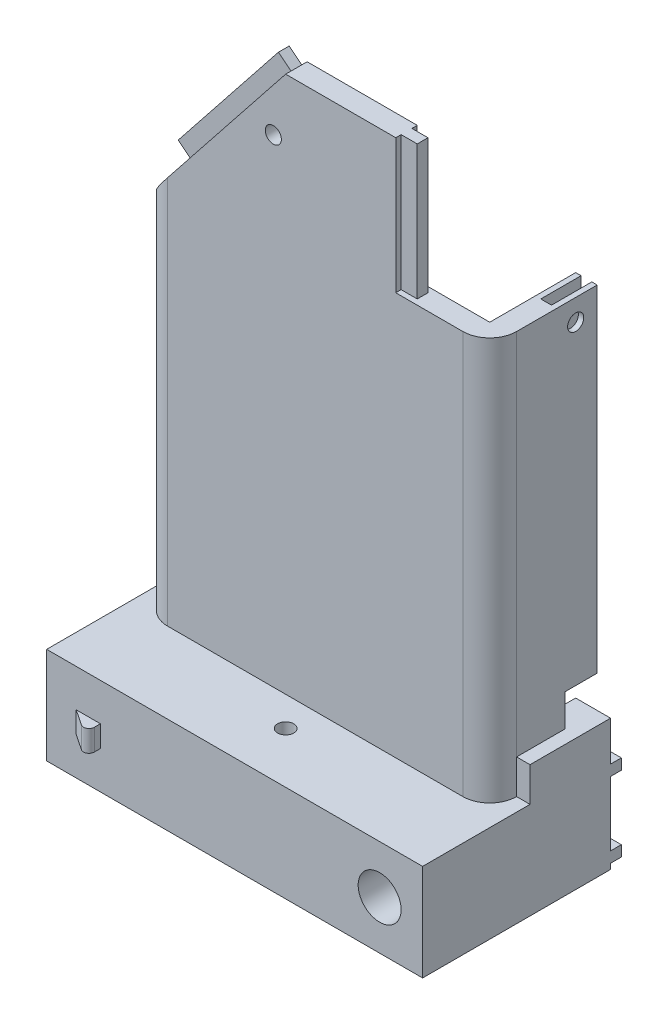
SolidWorks part; units mm, degrees
ref_plane "Front Plane" through (0, 0, 0) normal (0, 0, 1) x (1, 0, 0)
ref_plane "Top Plane" through (0, 0, 0) normal (0, 1, 0) x (1, 0, 0)
ref_plane "Right Plane" through (0, 0, 0) normal (1, 0, 0) x (0, 0, -1)
sketch "Sketch1" plane through (0, 0, 0) normal (0, 1, 0) x (1, 0, 0)
  line L1 (-32.5, -20) -> (32.5, -20)
  line L2 (-32.5, -20) -> (-32.5, 20)
  line L3 (-32.5, 20) -> (32.5, 20)
  line L4 (32.5, -20) -> (32.5, 20)
  line L5 (-32.5, -20) -> (32.5, 20) construction
  line L6 (-32.5, 20) -> (32.5, -20) construction
  point P0 (0, 0)
  dimension "D1" = 65
  dimension "D2" = 40
extrude "Boss-Extrude1" add sketch "Sketch1" along normal blind 100
shell "Shell1" thickness 4 removed face at (0, 0, 0) removed face at (0, 100, 0)
fillet "Fillet1" radius 5 4 edges at (32.5, 50, -20) (32.5, 50, 20) (-32.5, 50, -20) (-32.5, 50, 20)
sketch "Sketch2" plane through (0, 0, 0) normal (0, 0, 1) x (1, 0, 0)
  line L0 (-5.5, 100) -> (-32.5, 66)
  line L1 (28.5, 100) -> (-28.5, 100) construction
  line L2 (-32.5, 100) -> (-32.5, 0) construction
  line L3 (-32.5, 66) -> (-32.5, 100)
  line L4 (-32.5, 100) -> (-5.5, 100)
  dimension "D1" = 5.5
  dimension "D2" = 66
extrude "Cut-Extrude1" cut sketch "Sketch2" against normal through all both and the other way through all
sketch "Sketch3" plane through (0, 0, 0) normal (0, 0, 1) x (1, 0, 0)
  line L1 (32.5, 100) -> (15, 100)
  line L2 (32.5, 100) -> (32.5, 75)
  line L3 (32.5, 75) -> (15, 75)
  line L4 (15, 100) -> (15, 75)
  dimension "D1" = 25
  dimension "D2" = 17.5
extrude "Cut-Extrude2" cut sketch "Sketch3" against normal through all both and the other way through all
sketch "Sketch5" plane through (15, 0, 0) normal (1, 0, 0) x (0, 0, -1)
  line L0 (-18, 100) -> (-18, 75) construction
  line L1 (-16, 100) -> (-20, 100) construction
  line L2 (-16, 75) -> (-20, 75) construction
  line L4 (-19, 100) -> (-17, 100)
  line L5 (-19, 100) -> (-19, 75)
  line L6 (-19, 75) -> (-17, 75)
  line L7 (-17, 100) -> (-17, 75)
  dimension "D1" = 2
extrude "Boss-Extrude2" add sketch "Sketch5" along normal blind 3
mirror "Mirror1" about plane through (0, 0, 0) normal (0, 0, 1) of "Boss-Extrude2"
sketch "Sketch6" plane through (-52.0732, 41.3523, 0) normal (-0.7831, 0.6219, 0) x (0, 0, 1)
  line L0 (-18, 74.8907) -> (-18, 44.8907) construction
  line L1 (-20, 74.8907) -> (-16, 74.8907) construction
  line L3 (-19, 74.8907) -> (-17, 74.8907)
  line L4 (-19, 74.8907) -> (-19, 44.8907)
  line L5 (-19, 44.8907) -> (-17, 44.8907)
  line L6 (-17, 74.8907) -> (-17, 44.8907)
  dimension "D1" = 30
  dimension "D2" = 2
extrude "Boss-Extrude3" add sketch "Sketch6" along normal blind 3
mirror "Mirror2" about plane through (0, 0, 0) normal (0, 0, 1) of "Boss-Extrude3"
sketch "Sketch8" plane through (0, 0, 0) normal (0, 1, 0) x (1, 0, 0)
  line L1 (-35, -35) -> (35, -35)
  line L2 (-35, -35) -> (-35, 35)
  line L3 (-35, 35) -> (35, 35)
  line L4 (35, -35) -> (35, 35)
  line L5 (-35, -35) -> (35, 35) construction
  line L6 (-35, 35) -> (35, -35) construction
  point P0 (0, 0)
  dimension "D1" = 70
  dimension "D2" = 70
extrude "Boss-Extrude4" add sketch "Sketch8" against normal blind 18
sketch "Sketch10" plane through (-35, 0, 0) normal (-1, 0, 0) x (0, 0, 1)
  line L0 (-35, -9) -> (35, -9) construction
  line L1 (-30, -14) -> (30, -14)
  line L2 (-30, -14) -> (-30, -4)
  line L3 (-30, -4) -> (30, -4)
  line L4 (30, -14) -> (30, -4)
  line L5 (-30, -14) -> (30, -4) construction
  line L6 (-30, -4) -> (30, -14) construction
  line L7 (-35, -18) -> (-35, 0) construction
  line L8 (35, -18) -> (35, 0) construction
  line L9 (0, 0) -> (0, -18) construction
  line L10 (-35, -18) -> (35, -18) construction
  point P0 (0, -9)
  dimension "D1" = 60
  dimension "D2" = 10
extrude "Cut-Extrude4" cut sketch "Sketch10" against normal blind 45
sketch "Sketch23" plane through (0, 75, 0) normal (0, 1, 0) x (1, 0, 0)
  line L0 (0, 0) -> (32.5, 0) construction
  line L1 (29.5, 7.5) -> (31.5, 7.5)
  line L2 (29.5, 7.5) -> (29.5, -7.5)
  line L3 (29.5, -7.5) -> (31.5, -7.5)
  line L4 (31.5, 7.5) -> (31.5, -7.5)
  line L5 (32.5, 15) -> (32.5, -15) construction
  line L6 (28.5, 16) -> (28.5, -16) construction
  line L8 (30.5, 14.75) -> (30.5, -14.75) construction
  dimension "D1" = 2
  dimension "D2" = 15
extrude "Cut-Extrude10" cut sketch "Sketch23" against normal blind 10
sketch "Sketch24" plane through (32.5, 0, 0) normal (1, 0, 0) x (0, 0, -1)
  line L1 (15, 75) -> (-15, 75) construction
  circle A0 centre (-4, 71) radius 1.5
  point P2 (0, 75)
  dimension "D3" = 3
  dimension "D1" = 4
  dimension "D2" = 4
extrude "Cut-Extrude11" cut sketch "Sketch24" against normal blind 10 and the other way through all
mirror "Mirror4" about plane through (0, 0, 0) normal (0, 0, 1) of "Cut-Extrude11"
sketch "Sketch27" plane through (0, 0, 0) normal (0, 1, 0) x (1, 0, 0)
  line L0 (35, -35) -> (35, 35) construction
  line L1 (-35, 35) -> (35, 35)
  line L2 (-35, 35) -> (-35, 0)
  line L3 (-35, 0) -> (35, 0)
  line L4 (35, 35) -> (35, 0)
extrude "Cut-Extrude12" cut sketch "Sketch27" against normal through all both and the other way through all
sketch "Sketch29" plane through (0, 0, 0) normal (0, 0, -1) x (-1, 0, 0)
  line L0 (35, -2) -> (-35, -2) construction
  line L1 (35, -4) -> (35, 0) construction
  line L2 (-35, -18) -> (-35, 0) construction
  line L3 (35, -1) -> (-35, -1)
  line L4 (35, -1) -> (35, -3)
  line L5 (35, -3) -> (-35, -3)
  line L6 (-35, -1) -> (-35, -3)
  dimension "D1" = 2
extrude "Boss-Extrude6" add sketch "Sketch29" along normal blind 2
sketch "Sketch30" plane through (0, 0, 0) normal (0, 0, -1) x (-1, 0, 0)
  line L0 (35, -16) -> (-35, -16) construction
  line L1 (35, -18) -> (35, -14) construction
  line L2 (-35, -18) -> (-35, -3) construction
  line L4 (-35, -15) -> (35, -15)
  line L5 (-35, -15) -> (-35, -17)
  line L6 (-35, -17) -> (35, -17)
  line L7 (35, -15) -> (35, -17)
  dimension "D1" = 2
extrude "Boss-Extrude7" add sketch "Sketch30" along normal blind 2
sketch "Sketch31" plane through (0, 0, 35) normal (0, 0, 1) x (1, 0, 0)
  line L0 (35, -18) -> (35, 0) construction
  line L1 (-35, -18) -> (35, -18) construction
  circle A0 centre (27, -9) radius 2
  dimension "D1" = 4
  dimension "D2" = 8
  dimension "D3" = 9
extrude "Cut-Extrude13" cut sketch "Sketch31" against normal through all both and the other way through all
sketch "Sketch32" plane through (0, 0, 35) normal (0, 0, 1) x (1, 0, 0)
  circle A0 centre (27, -9) radius 4
  dimension "D1" = 8
extrude "Cut-Extrude14" cut sketch "Sketch32" against normal blind 15
sketch "Sketch34" plane through (0, 0, 0) normal (0, 1, 0) x (1, 0, 0)
  line L1 (-35, 0) -> (-35, -35) construction
  line L2 (-35, -35) -> (35, -35) construction
  circle A0 centre (0, -25.5) radius 1.5
  dimension "D1" = 3
  dimension "D2" = 9.5
  dimension "D3" = 35
extrude "Cut-Extrude15" cut sketch "Sketch34" against normal through all both and the other way through all
sketch "Sketch35" plane through (0, 0, 0) normal (0, 1, 0) x (1, 0, 0)
  line L1 (-35, 0) -> (35, 0) construction
  line L2 (28.5, -16) -> (28.5, 0) construction
  circle A0 centre (21, -10.5) radius 3
  dimension "D1" = 6
  dimension "D2" = 10.5
  dimension "D3" = 7.5
extrude "Boss-Extrude8" add sketch "Sketch35" along normal blind 7
sketch "Sketch36" plane through (0, 7, 0) normal (0, 1, 0) x (1, 0, 0)
  circle A0 centre (21, -10.5) radius 1.75
  dimension "D1" = 3.5
extrude "Cut-Extrude16" cut sketch "Sketch36" against normal blind 4
pattern_linear "LPattern1" count 2 spacing 43.5 along (-1, 0, 0) of "Boss-Extrude8", "Cut-Extrude16"
sketch "Sketch37" plane through (32.5, 0, 0) normal (1, 0, 0) x (0, 0, -1)
  line L0 (0, 0) -> (0, 75) construction
  line L1 (0, 12.4) -> (-6, 12.4)
  line L2 (0, 12.4) -> (0, 6.4)
  line L3 (0, 6.4) -> (-6, 6.4)
  line L4 (-6, 12.4) -> (-6, 6.4)
  line L5 (-15, 0) -> (0, 0) construction
  dimension "D1" = 6
  dimension "D2" = 6
  dimension "D3" = 6.4
extrude "Cut-Extrude17" cut sketch "Sketch37" against normal through all both and the other way through all
sketch "Sketch38" plane through (32.5, 0, 0) normal (1, 0, 0) x (0, 0, -1)
  line L1 (0, 6.4) -> (-15, 6.4)
  line L2 (0, 6.4) -> (0, 0)
  line L3 (0, 0) -> (-15, 0)
  line L4 (-15, 6.4) -> (-15, 0)
extrude "Boss-Extrude9" add sketch "Sketch38" along normal up to surface (2.5 mm away) up to face at (35, -9, 5.1667)
sketch "Sketch41" plane through (0, -18, 0) normal (0, -1, 0) x (-1, 0, 0)
  circle A0 centre (0, -25.5) radius 4
  dimension "D1" = 8
extrude "Cut-Extrude18" cut sketch "Sketch41" against normal blind 3
sketch "Sketch42" plane through (0, 0, 35) normal (0, 0, 1) x (1, 0, 0)
  line L0 (-35, -9) -> (35, -9) construction
  line L1 (-35, -18) -> (-35, 0) construction
  line L2 (35, -18) -> (35, 0) construction
  line L4 (-29.5, -7) -> (-25, -7)
  line L5 (-29.5, -7) -> (-29.5, -11)
  line L6 (-29.5, -11) -> (-25, -11)
  line L7 (-25, -7) -> (-25, -11)
  dimension "D1" = 4
  dimension "D2" = 4.5
  dimension "D3" = 5.5
extrude "Boss-Extrude10" add sketch "Sketch42" along normal blind 3
sketch "Sketch43" plane through (0, -7, 0) normal (0, 1, 0) x (1, 0, 0)
  line L0 (-25, -38) -> (-29.5, -35)
  line L1 (-29.5, -35) -> (-29.5, -38)
  line L2 (-29.5, -38) -> (-25, -38)
extrude "Cut-Extrude19" cut sketch "Sketch43" against normal through all contours L2 L0 L1
fillet "Fillet2" radius 1 1 edges at (-25, -9, 38)
sketch "Sketch46" plane through (0, 0, 20) normal (0, 0, 1) x (1, 0, 0)
  line L0 (-27.5, 72.2963) -> (-5.5, 100) construction
  line L1 (-7.8033, 89.0595) -> (-11.7188, 92.1689) construction
  line L2 (-5.5, 100) -> (-24.1565, 76.5067) construction
  circle A0 centre (-7.8033, 89.0595) radius 1.5
  dimension "D1" = 5
  dimension "D2" = 3
  dimension "D3" = 10
  dimension "D4" = 5
extrude "Cut-Extrude20" cut sketch "Sketch46" against normal blind 10
